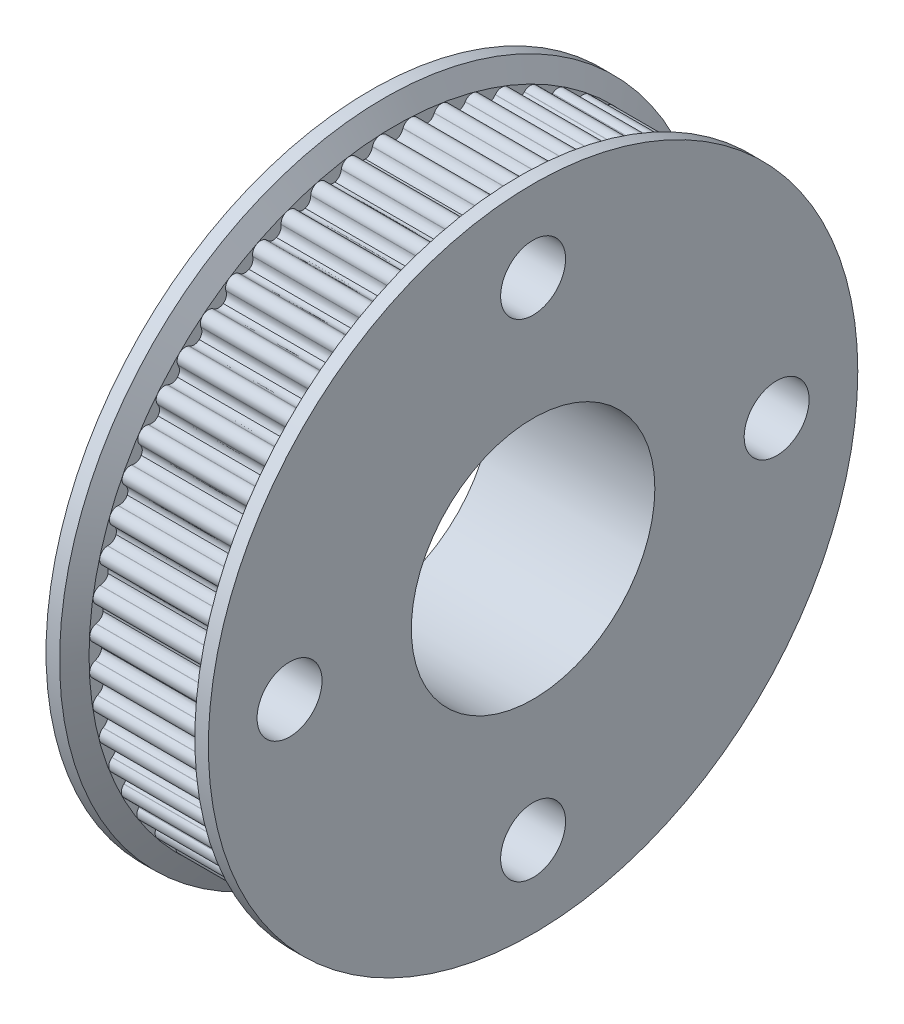
SolidWorks part; units mm, degrees
ref_plane "Front Plane" through (0, 0, 0) normal (0, 0, 1) x (1, 0, 0)
ref_plane "Top Plane" through (0, 0, 0) normal (0, 1, 0) x (1, 0, 0)
ref_plane "Right Plane" through (0, 0, 0) normal (1, 0, 0) x (0, 0, -1)
sketch "Sketch1" plane through (0, 0, 0) normal (0, 1, 0) x (1, 0, 0)
  line L0 (0, 0) -> (-29.5926, 0) construction
  line L1 (0, 7.5) -> (0, 8.9565)
  line L2 (-1.5, 18.85) -> (-8.5, 18.85)
  line L3 (-10, 20) -> (-10, 7.5)
  line L4 (-10, 7.5) -> (0, 7.5)
  line L5 (0, 8.9565) -> (0, 20)
  line L6 (-0.836, 20) -> (-1.5, 18.85)
  line L7 (-10, 4.001) -> (0, 4.001) construction
  line L8 (-5, 18.85) -> (-5, 12.6929) construction
  line L9 (-9.164, 20) -> (-8.5, 18.85)
  line L10 (-10, 20) -> (-8.5, 18.85) construction
  line L11 (-1.5, 18.85) -> (0, 8.9565) construction
  line L12 (-10, 20) -> (-9.164, 20)
  line L13 (-0.836, 20) -> (0, 20)
  point P15 (-5, 4.001)
  point P16 (0, 0)
  dimension "D1" = 10
  dimension "D2" = 7
  dimension "D3" = 37.7
  dimension "D4" = 40
  dimension "D5" = 15
  dimension "D6" = 120
revolve "Revolve1" add sketch "Sketch1" angle 360 about L0
ref_plane "Plane1" through (-1.5, 0, 0) normal (1, 0, 0) x (0, 0, -1)
ref_plane "Plane2" through (-8.5, 0, 0) normal (1, 0, 0) x (0, 0, -1)
sketch "Sketch3" plane through (-1.5, 0, 0) normal (1, 0, 0) x (0, 0, -1)
  line L0 (0.4895, 18.4804) -> (0.4858, 18.4697)
  line L1 (-0.4323, 18.471) -> (-0.436, 18.4817)
  line L2 (-1.3914, 18.4344) -> (-1.394, 18.4234)
  line L3 (-2.3607, 18.3247) -> (-2.3654, 18.3349)
  line L4 (-3.3107, 18.188) -> (-3.3122, 18.1768)
  line L5 (-4.2632, 17.9775) -> (-4.269, 17.9872)
  line L6 (-5.1937, 17.7423) -> (-5.194, 17.731)
  line L7 (-6.119, 17.4334) -> (-6.1258, 17.4424)
  line L8 (-7.0199, 17.1022) -> (-7.019, 17.0909)
  line L9 (-7.9078, 16.6983) -> (-7.9155, 16.7066)
  line L10 (-8.7691, 16.2747) -> (-8.767, 16.2636)
  line L11 (-9.6099, 15.7803) -> (-9.6184, 15.7877)
  line L12 (-10.4222, 15.269) -> (-10.419, 15.2581)
  line L13 (-11.2067, 14.6893) -> (-11.216, 14.6958)
  line L14 (-11.9612, 14.0959) -> (-11.9568, 14.0855)
  line L15 (-12.6808, 13.4374) -> (-12.6907, 13.4429)
  line L16 (-13.3691, 12.7684) -> (-13.3637, 12.7585)
  line L17 (-14.0159, 12.0383) -> (-14.0263, 12.0427)
  line L18 (-14.6305, 11.301) -> (-14.6241, 11.2917)
  line L19 (-15.1975, 10.5073) -> (-15.2083, 10.5106)
  line L20 (-15.7316, 9.7098) -> (-15.7243, 9.7012)
  line L21 (-16.2125, 8.8612) -> (-16.2236, 8.8633)
  line L22 (-16.6604, 8.0122) -> (-16.6522, 8.0044)
  line L23 (-17.05, 7.118) -> (-17.0612, 7.1189)
  line L24 (-17.4066, 6.2268) -> (-17.3977, 6.22)
  line L25 (-17.7006, 5.2968) -> (-17.7119, 5.2965)
  line L26 (-17.9621, 4.3732) -> (-17.9525, 4.3673)
  line L27 (-18.1573, 3.4175) -> (-18.1685, 3.4161)
  line L28 (-18.3209, 2.4717) -> (-18.3107, 2.4669)
  line L29 (-18.415, 1.5008) -> (-18.426, 1.4983)
  line L30 (-18.4789, 0.5431) -> (-18.4682, 0.5394)
  line L31 (-18.471, -0.4323) -> (-18.4817, -0.436)
  line L32 (-18.4344, -1.3914) -> (-18.4234, -1.394)
  line L33 (-18.3247, -2.3607) -> (-18.3349, -2.3654)
  line L34 (-18.188, -3.3107) -> (-18.1768, -3.3122)
  line L35 (-17.9775, -4.2632) -> (-17.9872, -4.269)
  line L36 (-17.7423, -5.1937) -> (-17.731, -5.194)
  line L37 (-17.4334, -6.119) -> (-17.4424, -6.1258)
  line L38 (-17.1022, -7.0199) -> (-17.0909, -7.019)
  line L39 (-16.6983, -7.9078) -> (-16.7066, -7.9155)
  line L40 (-16.2747, -8.7691) -> (-16.2636, -8.767)
  line L41 (-15.7803, -9.6099) -> (-15.7877, -9.6184)
  line L42 (-15.269, -10.4222) -> (-15.2581, -10.419)
  line L43 (-14.6893, -11.2067) -> (-14.6958, -11.216)
  line L44 (-14.0959, -11.9612) -> (-14.0855, -11.9568)
  line L45 (-13.4374, -12.6808) -> (-13.4429, -12.6907)
  line L46 (-12.7684, -13.3691) -> (-12.7585, -13.3637)
  line L47 (-12.0383, -14.0159) -> (-12.0427, -14.0263)
  line L48 (-11.301, -14.6305) -> (-11.2917, -14.6241)
  line L49 (-10.5073, -15.1975) -> (-10.5106, -15.2083)
  line L50 (-9.7098, -15.7316) -> (-9.7012, -15.7243)
  line L51 (-8.8612, -16.2125) -> (-8.8633, -16.2236)
  line L52 (-8.0122, -16.6604) -> (-8.0044, -16.6522)
  line L53 (-7.118, -17.05) -> (-7.1189, -17.0612)
  line L54 (-6.2268, -17.4066) -> (-6.22, -17.3977)
  line L55 (-5.2968, -17.7006) -> (-5.2965, -17.7119)
  line L56 (-4.3732, -17.9621) -> (-4.3673, -17.9525)
  line L57 (-3.4175, -18.1573) -> (-3.4161, -18.1685)
  line L58 (-2.4717, -18.3209) -> (-2.4669, -18.3107)
  line L59 (-1.5008, -18.415) -> (-1.4983, -18.426)
  line L60 (-0.5431, -18.4789) -> (-0.5394, -18.4682)
  line L61 (0.4323, -18.471) -> (0.436, -18.4817)
  line L62 (1.3914, -18.4344) -> (1.394, -18.4234)
  line L63 (2.3607, -18.3247) -> (2.3654, -18.3349)
  line L64 (3.3107, -18.188) -> (3.3122, -18.1768)
  line L65 (4.2632, -17.9775) -> (4.269, -17.9872)
  line L66 (5.1937, -17.7423) -> (5.194, -17.731)
  line L67 (6.119, -17.4334) -> (6.1258, -17.4424)
  line L68 (7.0199, -17.1022) -> (7.019, -17.0909)
  line L69 (7.9078, -16.6983) -> (7.9155, -16.7066)
  line L70 (8.7691, -16.2747) -> (8.767, -16.2636)
  line L71 (9.6099, -15.7803) -> (9.6184, -15.7877)
  line L72 (10.4222, -15.269) -> (10.419, -15.2581)
  line L73 (11.2067, -14.6893) -> (11.216, -14.6958)
  line L74 (11.9612, -14.0959) -> (11.9568, -14.0855)
  line L75 (12.6808, -13.4374) -> (12.6907, -13.4429)
  line L76 (13.3691, -12.7684) -> (13.3637, -12.7585)
  line L77 (14.0159, -12.0383) -> (14.0263, -12.0427)
  line L78 (14.6305, -11.301) -> (14.6241, -11.2917)
  line L79 (15.1975, -10.5073) -> (15.2083, -10.5106)
  line L80 (15.7316, -9.7098) -> (15.7243, -9.7012)
  line L81 (16.2125, -8.8612) -> (16.2236, -8.8633)
  line L82 (16.6604, -8.0122) -> (16.6522, -8.0044)
  line L83 (17.05, -7.118) -> (17.0612, -7.1189)
  line L84 (17.4066, -6.2268) -> (17.3977, -6.22)
  line L85 (17.7006, -5.2968) -> (17.7119, -5.2965)
  line L86 (17.9621, -4.3732) -> (17.9525, -4.3673)
  line L87 (18.1573, -3.4175) -> (18.1685, -3.4161)
  line L88 (18.3209, -2.4717) -> (18.3107, -2.4669)
  line L89 (18.415, -1.5008) -> (18.426, -1.4983)
  line L90 (18.4789, -0.5431) -> (18.4682, -0.5394)
  line L91 (18.471, 0.4323) -> (18.4817, 0.436)
  line L92 (18.4344, 1.3914) -> (18.4234, 1.394)
  line L93 (18.3247, 2.3607) -> (18.3349, 2.3654)
  line L94 (18.188, 3.3107) -> (18.1768, 3.3122)
  line L95 (17.9775, 4.2632) -> (17.9872, 4.269)
  line L96 (17.7423, 5.1937) -> (17.731, 5.194)
  line L97 (17.4334, 6.119) -> (17.4424, 6.1258)
  line L98 (17.1022, 7.0199) -> (17.0909, 7.019)
  line L99 (16.6983, 7.9078) -> (16.7066, 7.9155)
  line L100 (16.2747, 8.7691) -> (16.2636, 8.767)
  line L101 (15.7803, 9.6099) -> (15.7877, 9.6184)
  line L102 (15.269, 10.4222) -> (15.2581, 10.419)
  line L103 (14.6893, 11.2067) -> (14.6958, 11.216)
  line L104 (14.0959, 11.9612) -> (14.0855, 11.9568)
  line L105 (13.4374, 12.6808) -> (13.4429, 12.6907)
  line L106 (12.7684, 13.3691) -> (12.7585, 13.3637)
  line L107 (12.0383, 14.0159) -> (12.0427, 14.0263)
  line L108 (11.301, 14.6305) -> (11.2917, 14.6241)
  line L109 (10.5073, 15.1975) -> (10.5106, 15.2083)
  line L110 (9.7098, 15.7316) -> (9.7012, 15.7243)
  line L111 (8.8141, 16.2382) -> (8.8162, 16.2492)
  line L112 (7.9639, 16.6835) -> (7.9561, 16.6753)
  line L113 (7.0685, 17.0705) -> (7.0694, 17.0818)
  line L114 (6.1763, 17.4246) -> (6.1695, 17.4156)
  line L115 (5.2454, 17.7159) -> (5.2452, 17.7272)
  line L116 (4.3211, 17.9748) -> (4.3153, 17.9651)
  line L117 (3.3649, 18.1671) -> (3.3634, 18.1783)
  line L118 (2.4186, 18.328) -> (2.4138, 18.3178)
  line L119 (1.4475, 18.4193) -> (1.4449, 18.4303)
  arc A0 (-0.436, 18.4817) -> (-1.3914, 18.4344) centre (-0.9065, 18.3126) ccw
  arc A1 (-2.3654, 18.3349) -> (-3.3107, 18.188) centre (-2.8157, 18.1175) ccw
  arc A2 (-4.269, 17.9872) -> (-5.1937, 17.7423) centre (-4.6941, 17.7239) ccw
  arc A3 (-6.1258, 17.4424) -> (-7.0199, 17.1022) centre (-6.521, 17.1362) ccw
  arc A4 (-7.9155, 16.7066) -> (-8.7691, 16.2747) centre (-8.2765, 16.3607) ccw
  arc A5 (-9.6184, 15.7877) -> (-10.4222, 15.269) centre (-9.9413, 15.4059) ccw
  arc A6 (-11.216, 14.6958) -> (-11.9612, 14.0959) centre (-11.4972, 14.2824) ccw
  arc A7 (-12.6907, 13.4429) -> (-13.3691, 12.7684) centre (-12.9272, 13.0023) ccw
  arc A8 (-14.0263, 12.0427) -> (-14.6305, 11.301) centre (-14.2155, 11.5798) ccw
  arc A9 (-15.2083, 10.5106) -> (-15.7316, 9.7098) centre (-15.348, 10.0305) ccw
  arc A10 (-16.2236, 8.8633) -> (-16.6604, 8.0122) centre (-16.3124, 8.3712) ccw
  arc A11 (-17.0612, 7.1189) -> (-17.4066, 6.2268) centre (-17.0981, 6.6203) ccw
  arc A12 (-17.7119, 5.2965) -> (-17.9621, 4.3732) centre (-17.6964, 4.7968) ccw
  arc A13 (-18.1685, 3.4161) -> (-18.3209, 2.4717) centre (-18.1009, 2.9207) ccw
  arc A14 (-18.426, 1.4983) -> (-18.4789, 0.5431) centre (-18.307, 1.0127) ccw
  arc A15 (-18.4817, -0.436) -> (-18.4344, -1.3914) centre (-18.3126, -0.9065) ccw
  arc A16 (-18.3349, -2.3654) -> (-18.188, -3.3107) centre (-18.1175, -2.8157) ccw
  arc A17 (-17.9872, -4.269) -> (-17.7423, -5.1937) centre (-17.7239, -4.6941) ccw
  arc A18 (-17.4424, -6.1258) -> (-17.1022, -7.0199) centre (-17.1362, -6.521) ccw
  arc A19 (-16.7066, -7.9155) -> (-16.2747, -8.7691) centre (-16.3607, -8.2765) ccw
  arc A20 (-15.7877, -9.6184) -> (-15.269, -10.4222) centre (-15.4059, -9.9413) ccw
  arc A21 (-14.6958, -11.216) -> (-14.0959, -11.9612) centre (-14.2824, -11.4972) ccw
  arc A22 (-13.4429, -12.6907) -> (-12.7684, -13.3691) centre (-13.0023, -12.9272) ccw
  arc A23 (-12.0427, -14.0263) -> (-11.301, -14.6305) centre (-11.5798, -14.2155) ccw
  arc A24 (-10.5106, -15.2083) -> (-9.7098, -15.7316) centre (-10.0305, -15.348) ccw
  arc A25 (-8.8633, -16.2236) -> (-8.0122, -16.6604) centre (-8.3712, -16.3124) ccw
  arc A26 (-7.1189, -17.0612) -> (-6.2268, -17.4066) centre (-6.6203, -17.0981) ccw
  arc A27 (-5.2965, -17.7119) -> (-4.3732, -17.9621) centre (-4.7968, -17.6964) ccw
  arc A28 (-3.4161, -18.1685) -> (-2.4717, -18.3209) centre (-2.9207, -18.1009) ccw
  arc A29 (-1.4983, -18.426) -> (-0.5431, -18.4789) centre (-1.0127, -18.307) ccw
  arc A30 (0.436, -18.4817) -> (1.3914, -18.4344) centre (0.9065, -18.3126) ccw
  arc A31 (2.3654, -18.3349) -> (3.3107, -18.188) centre (2.8157, -18.1175) ccw
  arc A32 (4.269, -17.9872) -> (5.1937, -17.7423) centre (4.6941, -17.7239) ccw
  arc A33 (6.1258, -17.4424) -> (7.0199, -17.1022) centre (6.521, -17.1362) ccw
  arc A34 (7.9155, -16.7066) -> (8.7691, -16.2747) centre (8.2765, -16.3607) ccw
  arc A35 (9.6184, -15.7877) -> (10.4222, -15.269) centre (9.9413, -15.4059) ccw
  arc A36 (11.216, -14.6958) -> (11.9612, -14.0959) centre (11.4972, -14.2824) ccw
  arc A37 (12.6907, -13.4429) -> (13.3691, -12.7684) centre (12.9272, -13.0023) ccw
  arc A38 (14.0263, -12.0427) -> (14.6305, -11.301) centre (14.2155, -11.5798) ccw
  arc A39 (15.2083, -10.5106) -> (15.7316, -9.7098) centre (15.348, -10.0305) ccw
  arc A40 (16.2236, -8.8633) -> (16.6604, -8.0122) centre (16.3124, -8.3712) ccw
  arc A41 (17.0612, -7.1189) -> (17.4066, -6.2268) centre (17.0981, -6.6203) ccw
  arc A42 (17.7119, -5.2965) -> (17.9621, -4.3732) centre (17.6964, -4.7968) ccw
  arc A43 (18.1685, -3.4161) -> (18.3209, -2.4717) centre (18.1009, -2.9207) ccw
  arc A44 (18.426, -1.4983) -> (18.4789, -0.5431) centre (18.307, -1.0127) ccw
  arc A45 (18.4817, 0.436) -> (18.4344, 1.3914) centre (18.3126, 0.9065) ccw
  arc A46 (18.3349, 2.3654) -> (18.188, 3.3107) centre (18.1175, 2.8157) ccw
  arc A47 (17.9872, 4.269) -> (17.7423, 5.1937) centre (17.7239, 4.6941) ccw
  arc A48 (17.4424, 6.1258) -> (17.1022, 7.0199) centre (17.1362, 6.521) ccw
  arc A49 (16.7066, 7.9155) -> (16.2747, 8.7691) centre (16.3607, 8.2765) ccw
  arc A50 (15.7877, 9.6184) -> (15.269, 10.4222) centre (15.4059, 9.9413) ccw
  arc A51 (14.6958, 11.216) -> (14.0959, 11.9612) centre (14.2824, 11.4972) ccw
  arc A52 (13.4429, 12.6907) -> (12.7684, 13.3691) centre (13.0023, 12.9272) ccw
  arc A53 (12.0427, 14.0263) -> (11.301, 14.6305) centre (11.5798, 14.2155) ccw
  arc A54 (10.5106, 15.2083) -> (9.7098, 15.7316) centre (10.0305, 15.348) ccw
  arc A55 (8.8162, 16.2492) -> (7.9639, 16.6835) centre (8.3239, 16.3366) ccw
  arc A56 (7.0694, 17.0818) -> (6.1763, 17.4246) centre (6.5707, 17.1172) ccw
  arc A57 (5.2452, 17.7272) -> (4.3211, 17.9748) centre (4.7454, 17.7103) ccw
  arc A58 (3.3634, 18.1783) -> (2.4186, 18.328) centre (2.8682, 18.1093) ccw
  arc A59 (1.4449, 18.4303) -> (0.4895, 18.4804) centre (0.9596, 18.3099) ccw
  circle A61 centre (0, 0) radius 18.335 construction
  spline S0 degree 3 poles (0.4858, 18.4697) (0.4077, 18.2495) (0.2403, 18.0862) (0.0262, 18.0851) knots 0 0 0 0 1 1 1 1
  spline S1 degree 3 poles (0.0262, 18.0851) (-0.1878, 18.0868) (-0.3548, 18.2506) (-0.4323, 18.471) knots 0 0 0 0 1 1 1 1
  spline S2 degree 3 poles (-1.394, 18.4234) (-1.4515, 18.1875) (-1.5982, 18.0156) (-1.8382, 17.9913) knots 0 0 0 0 1 1 1 1
  spline S3 degree 3 poles (-1.8382, 17.9913) (-2.0782, 17.9665) (-2.2567, 18.1053) (-2.3607, 18.3247) knots 0 0 0 0 1 1 1 1
  spline S4 degree 3 poles (-3.3122, 18.1768) (-3.3447, 17.9362) (-3.4726, 17.7498) (-3.7088, 17.7006) knots 0 0 0 0 1 1 1 1
  spline S5 degree 3 poles (-3.7088, 17.7006) (-3.9448, 17.6509) (-4.1368, 17.7702) (-4.2632, 17.9775) knots 0 0 0 0 1 1 1 1
  spline S6 degree 3 poles (-5.194, 17.731) (-5.2012, 17.4883) (-5.309, 17.2896) (-5.5387, 17.216) knots 0 0 0 0 1 1 1 1
  spline S7 degree 3 poles (-5.5387, 17.216) (-5.7682, 17.1418) (-5.9717, 17.2404) (-6.119, 17.4334) knots 0 0 0 0 1 1 1 1
  spline S8 degree 3 poles (-7.019, 17.0909) (-7.0007, 16.8488) (-7.0871, 16.6399) (-7.3079, 16.5427) knots 0 0 0 0 1 1 1 1
  spline S9 degree 3 poles (-7.3079, 16.5427) (-7.5284, 16.445) (-7.7411, 16.5218) (-7.9078, 16.6983) knots 0 0 0 0 1 1 1 1
  spline S10 degree 3 poles (-8.767, 16.2636) (-8.7236, 16.0248) (-8.7877, 15.808) (-8.9971, 15.6882) knots 0 0 0 0 1 1 1 1
  spline S11 degree 3 poles (-8.9971, 15.6882) (-9.2062, 15.568) (-9.4256, 15.6221) (-9.6099, 15.7803) knots 0 0 0 0 1 1 1 1
  spline S12 degree 3 poles (-10.419, 15.2581) (-10.3508, 15.0251) (-10.3919, 14.8028) (-10.5876, 14.6618) knots 0 0 0 0 1 1 1 1
  spline S13 degree 3 poles (-10.5876, 14.6618) (-10.783, 14.5204) (-11.007, 14.5513) (-11.2067, 14.6893) knots 0 0 0 0 1 1 1 1
  spline S14 degree 3 poles (-11.9568, 14.0855) (-11.8647, 13.8608) (-11.8823, 13.6355) (-12.0622, 13.4748) knots 0 0 0 0 1 1 1 1
  spline S15 degree 3 poles (-12.0622, 13.4748) (-12.2418, 13.3137) (-12.4677, 13.321) (-12.6808, 13.4374) knots 0 0 0 0 1 1 1 1
  spline S16 degree 3 poles (-13.3637, 12.7585) (-13.2485, 12.5447) (-13.2425, 12.3187) (-13.4046, 12.1401) knots 0 0 0 0 1 1 1 1
  spline S17 degree 3 poles (-13.4046, 12.1401) (-13.5664, 11.9611) (-13.7918, 11.9448) (-14.0159, 12.0383) knots 0 0 0 0 1 1 1 1
  spline S18 degree 3 poles (-14.6241, 11.2917) (-14.4872, 11.0912) (-14.4576, 10.867) (-14.6002, 10.6725) knots 0 0 0 0 1 1 1 1
  spline S19 degree 3 poles (-14.6002, 10.6725) (-14.7423, 10.4776) (-14.9648, 10.4378) (-15.1975, 10.5073) knots 0 0 0 0 1 1 1 1
  spline S20 degree 3 poles (-15.7243, 9.7012) (-15.5672, 9.5161) (-15.5143, 9.2963) (-15.6358, 9.0879) knots 0 0 0 0 1 1 1 1
  spline S21 degree 3 poles (-15.6358, 9.0879) (-15.7568, 8.8792) (-15.9739, 8.8163) (-16.2125, 8.8612) knots 0 0 0 0 1 1 1 1
  spline S22 degree 3 poles (-16.6522, 8.0044) (-16.4766, 7.8367) (-16.4011, 7.6237) (-16.5001, 7.4037) knots 0 0 0 0 1 1 1 1
  spline S23 degree 3 poles (-16.5001, 7.4037) (-16.5986, 7.1835) (-16.808, 7.0983) (-17.05, 7.118) knots 0 0 0 0 1 1 1 1
  spline S24 degree 3 poles (-17.3977, 6.22) (-17.2055, 6.0715) (-17.1081, 5.8675) (-17.1836, 5.6384) knots 0 0 0 0 1 1 1 1
  spline S25 degree 3 poles (-17.1836, 5.6384) (-17.2585, 5.4091) (-17.4579, 5.3025) (-17.7006, 5.2968) knots 0 0 0 0 1 1 1 1
  spline S26 degree 3 poles (-17.9525, 4.3673) (-17.7459, 4.2398) (-17.6277, 4.0471) (-17.6788, 3.8114) knots 0 0 0 0 1 1 1 1
  spline S27 degree 3 poles (-17.6788, 3.8114) (-17.7294, 3.5755) (-17.9165, 3.4486) (-18.1573, 3.4175) knots 0 0 0 0 1 1 1 1
  spline S28 degree 3 poles (-18.3107, 2.4669) (-18.0919, 2.3616) (-17.9542, 2.1823) (-17.9804, 1.9425) knots 0 0 0 0 1 1 1 1
  spline S29 degree 3 poles (-17.9804, 1.9425) (-18.006, 1.7027) (-18.1788, 1.5569) (-18.415, 1.5008) knots 0 0 0 0 1 1 1 1
  spline S30 degree 3 poles (-18.4682, 0.5394) (-18.2396, 0.4576) (-18.0839, 0.2937) (-18.0849, 0.0524) knots 0 0 0 0 1 1 1 1
  spline S31 degree 3 poles (-18.0849, 0.0524) (-18.0853, -0.1888) (-18.242, -0.3518) (-18.471, -0.4323) knots 0 0 0 0 1 1 1 1
  spline S32 degree 3 poles (-18.4234, -1.394) (-18.1875, -1.4515) (-18.0156, -1.5982) (-17.9913, -1.8382) knots 0 0 0 0 1 1 1 1
  spline S33 degree 3 poles (-17.9913, -1.8382) (-17.9665, -2.0782) (-18.1053, -2.2567) (-18.3247, -2.3607) knots 0 0 0 0 1 1 1 1
  spline S34 degree 3 poles (-18.1768, -3.3122) (-17.9362, -3.3447) (-17.7498, -3.4726) (-17.7006, -3.7088) knots 0 0 0 0 1 1 1 1
  spline S35 degree 3 poles (-17.7006, -3.7088) (-17.6509, -3.9448) (-17.7702, -4.1368) (-17.9775, -4.2632) knots 0 0 0 0 1 1 1 1
  spline S36 degree 3 poles (-17.731, -5.194) (-17.4883, -5.2012) (-17.2896, -5.309) (-17.216, -5.5387) knots 0 0 0 0 1 1 1 1
  spline S37 degree 3 poles (-17.216, -5.5387) (-17.1418, -5.7682) (-17.2404, -5.9717) (-17.4334, -6.119) knots 0 0 0 0 1 1 1 1
  spline S38 degree 3 poles (-17.0909, -7.019) (-16.8488, -7.0007) (-16.6399, -7.0871) (-16.5427, -7.3079) knots 0 0 0 0 1 1 1 1
  spline S39 degree 3 poles (-16.5427, -7.3079) (-16.445, -7.5284) (-16.5218, -7.7411) (-16.6983, -7.9078) knots 0 0 0 0 1 1 1 1
  spline S40 degree 3 poles (-16.2636, -8.767) (-16.0248, -8.7236) (-15.808, -8.7877) (-15.6882, -8.9971) knots 0 0 0 0 1 1 1 1
  spline S41 degree 3 poles (-15.6882, -8.9971) (-15.568, -9.2062) (-15.6221, -9.4256) (-15.7803, -9.6099) knots 0 0 0 0 1 1 1 1
  spline S42 degree 3 poles (-15.2581, -10.419) (-15.0251, -10.3508) (-14.8028, -10.3919) (-14.6618, -10.5876) knots 0 0 0 0 1 1 1 1
  spline S43 degree 3 poles (-14.6618, -10.5876) (-14.5204, -10.783) (-14.5513, -11.007) (-14.6893, -11.2067) knots 0 0 0 0 1 1 1 1
  spline S44 degree 3 poles (-14.0855, -11.9568) (-13.8608, -11.8647) (-13.6355, -11.8823) (-13.4748, -12.0622) knots 0 0 0 0 1 1 1 1
  spline S45 degree 3 poles (-13.4748, -12.0622) (-13.3137, -12.2418) (-13.321, -12.4677) (-13.4374, -12.6808) knots 0 0 0 0 1 1 1 1
  spline S46 degree 3 poles (-12.7585, -13.3637) (-12.5447, -13.2485) (-12.3187, -13.2425) (-12.1401, -13.4046) knots 0 0 0 0 1 1 1 1
  spline S47 degree 3 poles (-12.1401, -13.4046) (-11.9611, -13.5664) (-11.9448, -13.7918) (-12.0383, -14.0159) knots 0 0 0 0 1 1 1 1
  spline S48 degree 3 poles (-11.2917, -14.6241) (-11.0912, -14.4872) (-10.867, -14.4576) (-10.6725, -14.6002) knots 0 0 0 0 1 1 1 1
  spline S49 degree 3 poles (-10.6725, -14.6002) (-10.4776, -14.7423) (-10.4378, -14.9648) (-10.5073, -15.1975) knots 0 0 0 0 1 1 1 1
  spline S50 degree 3 poles (-9.7012, -15.7243) (-9.5161, -15.5672) (-9.2963, -15.5143) (-9.0879, -15.6358) knots 0 0 0 0 1 1 1 1
  spline S51 degree 3 poles (-9.0879, -15.6358) (-8.8792, -15.7568) (-8.8163, -15.9739) (-8.8612, -16.2125) knots 0 0 0 0 1 1 1 1
  spline S52 degree 3 poles (-8.0044, -16.6522) (-7.8367, -16.4766) (-7.6237, -16.4011) (-7.4037, -16.5001) knots 0 0 0 0 1 1 1 1
  spline S53 degree 3 poles (-7.4037, -16.5001) (-7.1835, -16.5986) (-7.0983, -16.808) (-7.118, -17.05) knots 0 0 0 0 1 1 1 1
  spline S54 degree 3 poles (-6.22, -17.3977) (-6.0715, -17.2055) (-5.8675, -17.1081) (-5.6384, -17.1836) knots 0 0 0 0 1 1 1 1
  spline S55 degree 3 poles (-5.6384, -17.1836) (-5.4091, -17.2585) (-5.3025, -17.4579) (-5.2968, -17.7006) knots 0 0 0 0 1 1 1 1
  spline S56 degree 3 poles (-4.3673, -17.9525) (-4.2398, -17.7459) (-4.0471, -17.6277) (-3.8114, -17.6788) knots 0 0 0 0 1 1 1 1
  spline S57 degree 3 poles (-3.8114, -17.6788) (-3.5755, -17.7294) (-3.4486, -17.9165) (-3.4175, -18.1573) knots 0 0 0 0 1 1 1 1
  spline S58 degree 3 poles (-2.4669, -18.3107) (-2.3616, -18.0919) (-2.1823, -17.9542) (-1.9425, -17.9804) knots 0 0 0 0 1 1 1 1
  spline S59 degree 3 poles (-1.9425, -17.9804) (-1.7027, -18.006) (-1.5569, -18.1788) (-1.5008, -18.415) knots 0 0 0 0 1 1 1 1
  spline S60 degree 3 poles (-0.5394, -18.4682) (-0.4576, -18.2396) (-0.2937, -18.0839) (-0.0524, -18.0849) knots 0 0 0 0 1 1 1 1
  spline S61 degree 3 poles (-0.0524, -18.0849) (0.1888, -18.0853) (0.3518, -18.242) (0.4323, -18.471) knots 0 0 0 0 1 1 1 1
  spline S62 degree 3 poles (1.394, -18.4234) (1.4515, -18.1875) (1.5982, -18.0156) (1.8382, -17.9913) knots 0 0 0 0 1 1 1 1
  spline S63 degree 3 poles (1.8382, -17.9913) (2.0782, -17.9665) (2.2567, -18.1053) (2.3607, -18.3247) knots 0 0 0 0 1 1 1 1
  spline S64 degree 3 poles (3.3122, -18.1768) (3.3447, -17.9362) (3.4726, -17.7498) (3.7088, -17.7006) knots 0 0 0 0 1 1 1 1
  spline S65 degree 3 poles (3.7088, -17.7006) (3.9448, -17.6509) (4.1368, -17.7702) (4.2632, -17.9775) knots 0 0 0 0 1 1 1 1
  spline S66 degree 3 poles (5.194, -17.731) (5.2012, -17.4883) (5.309, -17.2896) (5.5387, -17.216) knots 0 0 0 0 1 1 1 1
  spline S67 degree 3 poles (5.5387, -17.216) (5.7682, -17.1418) (5.9717, -17.2404) (6.119, -17.4334) knots 0 0 0 0 1 1 1 1
  spline S68 degree 3 poles (7.019, -17.0909) (7.0007, -16.8488) (7.0871, -16.6399) (7.3079, -16.5427) knots 0 0 0 0 1 1 1 1
  spline S69 degree 3 poles (7.3079, -16.5427) (7.5284, -16.445) (7.7411, -16.5218) (7.9078, -16.6983) knots 0 0 0 0 1 1 1 1
  spline S70 degree 3 poles (8.767, -16.2636) (8.7236, -16.0248) (8.7877, -15.808) (8.9971, -15.6882) knots 0 0 0 0 1 1 1 1
  spline S71 degree 3 poles (8.9971, -15.6882) (9.2062, -15.568) (9.4256, -15.6221) (9.6099, -15.7803) knots 0 0 0 0 1 1 1 1
  spline S72 degree 3 poles (10.419, -15.2581) (10.3508, -15.0251) (10.3919, -14.8028) (10.5876, -14.6618) knots 0 0 0 0 1 1 1 1
  spline S73 degree 3 poles (10.5876, -14.6618) (10.783, -14.5204) (11.007, -14.5513) (11.2067, -14.6893) knots 0 0 0 0 1 1 1 1
  spline S74 degree 3 poles (11.9568, -14.0855) (11.8647, -13.8608) (11.8823, -13.6355) (12.0622, -13.4748) knots 0 0 0 0 1 1 1 1
  spline S75 degree 3 poles (12.0622, -13.4748) (12.2418, -13.3137) (12.4677, -13.321) (12.6808, -13.4374) knots 0 0 0 0 1 1 1 1
  spline S76 degree 3 poles (13.3637, -12.7585) (13.2485, -12.5447) (13.2425, -12.3187) (13.4046, -12.1401) knots 0 0 0 0 1 1 1 1
  spline S77 degree 3 poles (13.4046, -12.1401) (13.5664, -11.9611) (13.7918, -11.9448) (14.0159, -12.0383) knots 0 0 0 0 1 1 1 1
  spline S78 degree 3 poles (14.6241, -11.2917) (14.4872, -11.0912) (14.4576, -10.867) (14.6002, -10.6725) knots 0 0 0 0 1 1 1 1
  spline S79 degree 3 poles (14.6002, -10.6725) (14.7423, -10.4776) (14.9648, -10.4378) (15.1975, -10.5073) knots 0 0 0 0 1 1 1 1
  spline S80 degree 3 poles (15.7243, -9.7012) (15.5672, -9.5161) (15.5143, -9.2963) (15.6358, -9.0879) knots 0 0 0 0 1 1 1 1
  spline S81 degree 3 poles (15.6358, -9.0879) (15.7568, -8.8792) (15.9739, -8.8163) (16.2125, -8.8612) knots 0 0 0 0 1 1 1 1
  spline S82 degree 3 poles (16.6522, -8.0044) (16.4766, -7.8367) (16.4011, -7.6237) (16.5001, -7.4037) knots 0 0 0 0 1 1 1 1
  spline S83 degree 3 poles (16.5001, -7.4037) (16.5986, -7.1835) (16.808, -7.0983) (17.05, -7.118) knots 0 0 0 0 1 1 1 1
  spline S84 degree 3 poles (17.3977, -6.22) (17.2055, -6.0715) (17.1081, -5.8675) (17.1836, -5.6384) knots 0 0 0 0 1 1 1 1
  spline S85 degree 3 poles (17.1836, -5.6384) (17.2585, -5.4091) (17.4579, -5.3025) (17.7006, -5.2968) knots 0 0 0 0 1 1 1 1
  spline S86 degree 3 poles (17.9525, -4.3673) (17.7459, -4.2398) (17.6277, -4.0471) (17.6788, -3.8114) knots 0 0 0 0 1 1 1 1
  spline S87 degree 3 poles (17.6788, -3.8114) (17.7294, -3.5755) (17.9165, -3.4486) (18.1573, -3.4175) knots 0 0 0 0 1 1 1 1
  spline S88 degree 3 poles (18.3107, -2.4669) (18.0919, -2.3616) (17.9542, -2.1823) (17.9804, -1.9425) knots 0 0 0 0 1 1 1 1
  spline S89 degree 3 poles (17.9804, -1.9425) (18.006, -1.7027) (18.1788, -1.5569) (18.415, -1.5008) knots 0 0 0 0 1 1 1 1
  spline S90 degree 3 poles (18.4682, -0.5394) (18.2396, -0.4576) (18.0839, -0.2937) (18.0849, -0.0524) knots 0 0 0 0 1 1 1 1
  spline S91 degree 3 poles (18.0849, -0.0524) (18.0853, 0.1888) (18.242, 0.3518) (18.471, 0.4323) knots 0 0 0 0 1 1 1 1
  spline S92 degree 3 poles (18.4234, 1.394) (18.1875, 1.4515) (18.0156, 1.5982) (17.9913, 1.8382) knots 0 0 0 0 1 1 1 1
  spline S93 degree 3 poles (17.9913, 1.8382) (17.9665, 2.0782) (18.1053, 2.2567) (18.3247, 2.3607) knots 0 0 0 0 1 1 1 1
  spline S94 degree 3 poles (18.1768, 3.3122) (17.9362, 3.3447) (17.7498, 3.4726) (17.7006, 3.7088) knots 0 0 0 0 1 1 1 1
  spline S95 degree 3 poles (17.7006, 3.7088) (17.6509, 3.9448) (17.7702, 4.1368) (17.9775, 4.2632) knots 0 0 0 0 1 1 1 1
  spline S96 degree 3 poles (17.731, 5.194) (17.4883, 5.2012) (17.2896, 5.309) (17.216, 5.5387) knots 0 0 0 0 1 1 1 1
  spline S97 degree 3 poles (17.216, 5.5387) (17.1418, 5.7682) (17.2404, 5.9717) (17.4334, 6.119) knots 0 0 0 0 1 1 1 1
  spline S98 degree 3 poles (17.0909, 7.019) (16.8488, 7.0007) (16.6399, 7.0871) (16.5427, 7.3079) knots 0 0 0 0 1 1 1 1
  spline S99 degree 3 poles (16.5427, 7.3079) (16.445, 7.5284) (16.5218, 7.7411) (16.6983, 7.9078) knots 0 0 0 0 1 1 1 1
  spline S100 degree 3 poles (16.2636, 8.767) (16.0248, 8.7236) (15.808, 8.7877) (15.6882, 8.9971) knots 0 0 0 0 1 1 1 1
  spline S101 degree 3 poles (15.6882, 8.9971) (15.568, 9.2062) (15.6221, 9.4256) (15.7803, 9.6099) knots 0 0 0 0 1 1 1 1
  spline S102 degree 3 poles (15.2581, 10.419) (15.0251, 10.3508) (14.8028, 10.3919) (14.6618, 10.5876) knots 0 0 0 0 1 1 1 1
  spline S103 degree 3 poles (14.6618, 10.5876) (14.5204, 10.783) (14.5513, 11.007) (14.6893, 11.2067) knots 0 0 0 0 1 1 1 1
  spline S104 degree 3 poles (14.0855, 11.9568) (13.8608, 11.8647) (13.6355, 11.8823) (13.4748, 12.0622) knots 0 0 0 0 1 1 1 1
  spline S105 degree 3 poles (13.4748, 12.0622) (13.3137, 12.2418) (13.321, 12.4677) (13.4374, 12.6808) knots 0 0 0 0 1 1 1 1
  spline S106 degree 3 poles (12.7585, 13.3637) (12.5447, 13.2485) (12.3187, 13.2425) (12.1401, 13.4046) knots 0 0 0 0 1 1 1 1
  spline S107 degree 3 poles (12.1401, 13.4046) (11.9611, 13.5664) (11.9448, 13.7918) (12.0383, 14.0159) knots 0 0 0 0 1 1 1 1
  spline S108 degree 3 poles (11.2917, 14.6241) (11.0912, 14.4872) (10.867, 14.4576) (10.6725, 14.6002) knots 0 0 0 0 1 1 1 1
  spline S109 degree 3 poles (10.6725, 14.6002) (10.4776, 14.7423) (10.4378, 14.9648) (10.5073, 15.1975) knots 0 0 0 0 1 1 1 1
  spline S110 degree 3 poles (9.7012, 15.7243) (9.5161, 15.5672) (9.5993, 15.3388) (9.0425, 15.6621) knots 0 0 0 0 1 1 1 1
  spline S111 degree 3 poles (9.0425, 15.6621) (8.8334, 15.7824) (8.77, 15.9994) (8.8141, 16.2382) knots 0 0 0 0 1 1 1 1
  spline S112 degree 3 poles (7.9561, 16.6753) (7.7889, 16.4993) (7.5761, 16.4231) (7.3558, 16.5215) knots 0 0 0 0 1 1 1 1
  spline S113 degree 3 poles (7.3558, 16.5215) (7.1353, 16.6193) (7.0495, 16.8285) (7.0685, 17.0705) knots 0 0 0 0 1 1 1 1
  spline S114 degree 3 poles (6.1695, 17.4156) (6.0216, 17.2231) (5.8179, 17.125) (5.5886, 17.1999) knots 0 0 0 0 1 1 1 1
  spline S115 degree 3 poles (5.5886, 17.1999) (5.3591, 17.2741) (5.2519, 17.4732) (5.2454, 17.7159) knots 0 0 0 0 1 1 1 1
  spline S116 degree 3 poles (4.3153, 17.9651) (4.1883, 17.7581) (3.996, 17.6394) (3.7601, 17.6898) knots 0 0 0 0 1 1 1 1
  spline S117 degree 3 poles (3.7601, 17.6898) (3.5241, 17.7397) (3.3967, 17.9264) (3.3649, 18.1671) knots 0 0 0 0 1 1 1 1
  spline S118 degree 3 poles (2.4138, 18.3178) (2.3091, 18.0986) (2.1303, 17.9604) (1.8904, 17.9859) knots 0 0 0 0 1 1 1 1
  spline S119 degree 3 poles (1.8904, 17.9859) (1.6505, 18.0109) (1.5042, 18.1832) (1.4475, 18.4193) knots 0 0 0 0 1 1 1 1
extrude "Cut-Extrude4" cut sketch "Sketch3" against normal up to surface (7 mm away) flip side to cut up to plane "Plane2"
sketch "Sketch6" plane through (-10, 0, 0) normal (-1, 0, 0) x (0, 0, 1)
  circle A0 centre (0, 15) radius 2
  circle A1 centre (15, 0) radius 2
  circle A2 centre (0, -15) radius 2
  circle A3 centre (-15, 0) radius 2
  point P12 (0, 0)
  dimension "D1" = 4
  dimension "D2" = 15
  dimension "D3" = 4
extrude "Cut-Extrude5" cut sketch "Sketch6" against normal up to surface (10 mm away) up to face at (0, 0, -20)
sketch "Sketch7" plane through (-10, 0, 0) normal (-1, 0, 0) x (0, 0, 1)
  circle A0 centre (0, 15) radius 3
  circle A1 centre (15, 0) radius 3
  circle A2 centre (0, -15) radius 3
  circle A3 centre (-15, 0) radius 3
  point P12 (0, 0)
  dimension "D1" = 6
  dimension "D2" = 4
extrude "Cut-Extrude6" cut sketch "Sketch7" against normal blind 3
